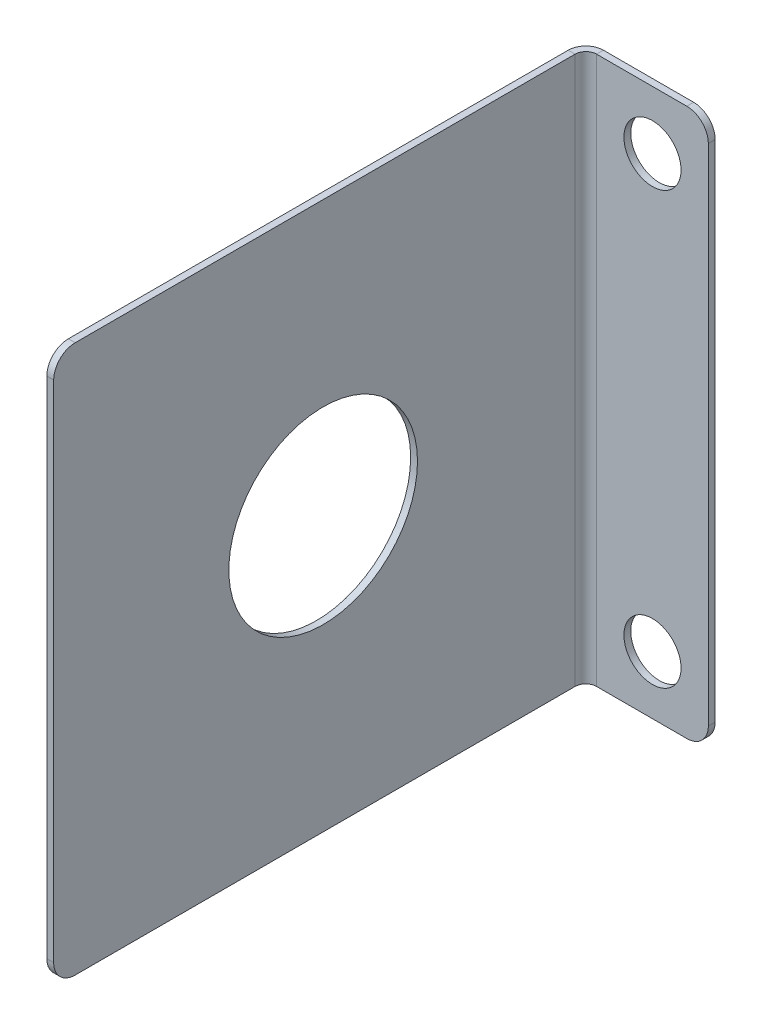
SolidWorks part; units mm, degrees
note: The reader was unsure of these and kept them because the rebuilt part matched: flange length of "Edge-Flange1".
ref_plane "Front Plane" through (0, 0, 0) normal (0, 0, 1) x (1, 0, 0)
ref_plane "Top Plane" through (0, 0, 0) normal (0, 1, 0) x (1, 0, 0)
ref_plane "Right Plane" through (0, 0, 0) normal (1, 0, 0) x (0, 0, -1)
sketch "Sketch1" plane through (0, 0, 0) normal (1, 0, 0) x (0, 0, -1)
  line L1 (-25, -25.4) -> (25, -25.4)
  line L2 (-25, -25.4) -> (-25, 25.4)
  line L3 (-25, 25.4) -> (25, 25.4)
  line L4 (25, -25.4) -> (25, 25.4)
  line L5 (-25, -25.4) -> (25, 25.4) construction
  line L6 (-25, 25.4) -> (25, -25.4) construction
  point P0 (0, 0)
  dimension "D1" = 50.8
  dimension "D2" = 50
base flange "Base-Flange1" sketch "Sketch1" thickness 0.635 reverse thickness direction no parameters "D1"=1
sketch "Sketch9" plane through (0, 0, 0) normal (1, 0, 0) x (0, 0, -1)
  circle A0 centre (0, 0) radius 8.75
  point P2 (9.0686, 0)
  point P3 (0, 0)
  dimension "D2" = 17.5
  dimension "D1" = 0
extrude "Cut-Extrude1" cut sketch "Sketch9" against normal through all normal cut yes
edge flange "Edge-Flange1" sketch "Sketch12" flange angle 90 flange length 12 flange position material inside bend radius 1 thickness 0.635 relief rectangular parameters "D6"=10
sketch "Sketch12" plane through (0, 0, -25) normal (0, 0, -1) x (0, 1, 0)
  line L0 (-25.4, 0) -> (25.4, 0) construction
  line L1 (-25.4, 0) -> (25.4, 0)
  line L2 (-25.4, 0) -> (-25.4, 11.365)
  line L3 (-25.4, 11.365) -> (25.4, 11.365)
  line L4 (25.4, 11.365) -> (25.4, 0)
bend "EdgeBend1" bend radius 1 bend angle 90 parameters "D5"=1
sketch "Sketch13" plane through (0, 0, -24.365) normal (0, 0, 1) x (1, 0, 0)
  line L0 (6.1825, 25.4) -> (6.1825, -25.4) construction
  line L1 (1, 25.4) -> (11.365, 25.4) construction
  line L2 (11.365, -25.4) -> (1, -25.4) construction
  circle A0 centre (6.1825, -20) radius 2.65
  circle A3 centre (6.1825, 20) radius 2.65
  dimension "D3" = 5.3
  dimension "D2" = 5.3
  dimension "D1" = 20
  dimension "D5" = 20
extrude "Cut-Extrude2" cut sketch "Sketch13" against normal through all normal cut yes
fillet "Fillet1" radius 2 4 edges at (11.365, -25.4, -24.6825) (11.365, 25.4, -24.6825) (-0.3175, 25.4, 25) (-0.3175, -25.4, 25)
sketch "Bend-Lines1" [suppressed] plane through (0, 0, 0) normal (0, 1, 0) x (1, 0, 0)
sketch "Bounding-Box1" [suppressed] plane through (0, 0, 0) normal (0, 1, 0) x (1, 0, 0)
sheet metal parameters "Sheet-Metal1" thickness 0.635 parameters "D1"=1
flat pattern "Flat-Pattern1" [suppressed]
sketch "Bend-Lines2" plane through (0, 0, 0) normal (0, 1, 0) x (1, 0, 0)
sketch3d "Bounding-Box2" [suppressed]
  line L0 (-25, -10, 0) -> (25, -10, 0) construction
  line L1 (-25, 10, 0) -> (25, 10, 0) construction
  line L2 (-25, -10, 0) -> (-25, 10, 0) construction
  line L3 (25, -10, 0) -> (25, 10, 0) construction
sheet metal parameters "Sheet-Metal3" thickness 0.635 parameters "D1"=1
flat pattern "Flat-Pattern1"
sketch "Bend-Lines2" plane through (0, 0, 0) normal (1, 0, 0) x (0, 0, -1)
  point P0 (-25.4, -19.3998)
  point P1 (25.4, -19.3998)
sketch3d "Bounding-Box2" [suppressed]
  line L0 (25.4, -20, 0) -> (-25.4, -20, 0) construction
  line L1 (25.4, 20, 0) -> (-25.4, 20, 0) construction
  line L2 (25.4, -20, 0) -> (25.4, 20, 0) construction
  line L3 (-25.4, -20, 0) -> (-25.4, 20, 0) construction
sheet metal parameters "Sheet-Metal5" thickness 0.635 parameters "D1"=1
flat pattern "Flat-Pattern1"
sketch "Bend-Lines2" plane through (0, 0, 0) normal (1, 0, 0) x (0, 0, -1)
  line L0 (29.3998, -15) -> (29.3998, 15) construction
  line L1 (29.3998, -15) -> (29.3998, 15) construction
sketch3d "Bounding-Box2" [suppressed]
  line L0 (40.7995, -15, 0) -> (-30, -15, 0) construction
  line L1 (40.7995, 15, 0) -> (-30, 15, 0) construction
  line L2 (40.7995, -15, 0) -> (40.7995, 15, 0) construction
  line L3 (-30, -15, 0) -> (-30, 15, 0) construction
bend of the flat pattern "Flatten-<EdgeBend1>1"
sheet metal parameters "Sheet-Metal6" thickness 0.635 parameters "D1"=1
flat pattern "Flat-Pattern1"
sketch "Bend-Lines2" plane through (0, 0, 0) normal (1, 0, 0) x (0, 0, -1)
  line L0 (24.3998, -25.4) -> (24.3998, 25.4) construction
  line L1 (24.3998, -25.4) -> (24.3998, 25.4) construction
sketch3d "Bounding-Box2" [suppressed]
  line L0 (35.7995, -25.4, 0) -> (-25, -25.4, 0) construction
  line L1 (35.7995, 25.4, 0) -> (-25, 25.4, 0) construction
  line L2 (35.7995, -25.4, 0) -> (35.7995, 25.4, 0) construction
  line L3 (-25, -25.4, 0) -> (-25, 25.4, 0) construction
bend of the flat pattern "Flatten-<EdgeBend1>1"
